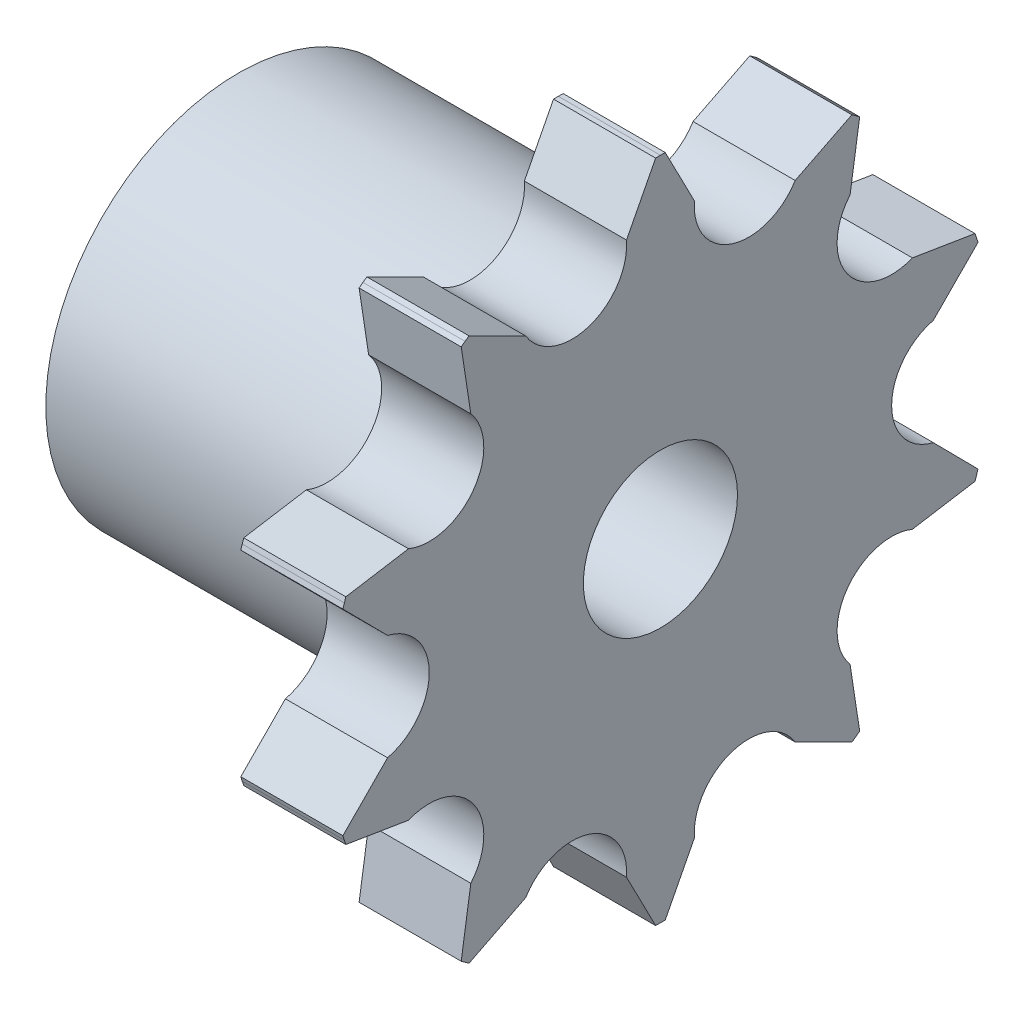
SolidWorks part; units mm, degrees
ref_plane "Front Plane" through (0, 0, 0) normal (0, 0, 1) x (1, 0, 0)
ref_plane "Top Plane" through (0, 0, 0) normal (0, 1, 0) x (1, 0, 0)
ref_plane "Right Plane" through (0, 0, 0) normal (1, 0, 0) x (0, 0, -1)
sketch "Sketch1" plane through (0, 0, 0) normal (1, 0, 0) x (0, 0, -1)
  line L0 (0, 0) -> (0, 17.25)
  line L1 (0, 0) -> (10.1393, 13.9555)
  line L4 (10.1393, 13.9555) -> (9.936, 14.101)
  line L5 (9.936, 14.101) -> (6.9922, 12.6205)
  line L6 (0, 0) -> (3.7082, 11.4127) construction
  line L7 (0.25, 17.2482) -> (1.7614, 14.3201)
  line L8 (10.1393, 13.9555) -> (10.2862, 14.1578)
  line L9 (0, 17.25) -> (0, 17.5)
  circle A0 centre (0, 0) radius 12
  circle A1 centre (0, 0) radius 17.25
  circle A2 centre (0, 0) radius 14.4281 construction
  arc A3 (1.7614, 14.3201) -> (6.9922, 12.6205) centre (4.5826, 14.1037) ccw
  circle A4 centre (0, 0) radius 17.5
  point P10 (10.0376, 14.0283)
  point P13 (0.125, 17.2491)
  dimension "D1" = 24
  dimension "D2" = 34.5
  dimension "D3" = 0.25
  dimension "D6" = 35
  dimension "D4" = 36
  dimension "D5" = 5.5
extrude "Boss-Extrude1" add sketch "Sketch1" along normal blind 5.3 contours L1 A0 L0 | A3 A0 L1 L4 L5 | A3 L7 A1 L0 A0 region at (0, 7.4839, -2.4317) region at (0, 13.8822, -0.9253) region at (0, 11.7748, -7.4111)
pattern_circular "CirPattern2" count 10 over 360 about axis through (5.3, 0, 0) along (-1, 0, 0) of "Boss-Extrude1" reverse direction yes
sketch "Sketch2" plane through (0, 0, 0) normal (-1, 0, 0) x (0, 0, 1)
  circle A0 centre (0, 0) radius 4
  circle A1 centre (0, 0) radius 10
  dimension "D1" = 8
  dimension "D2" = 20
extrude "Boss-Extrude2" add sketch "Sketch2" along normal blind 16.6
extrude "Cut-Extrude2" cut sketch "Sketch2<2>" against normal blind 16.6 contours A0 region at (0, 0, 0)
sketch "Sketch2<2>" plane through (0, 0, 0) normal (-1, 0, 0) x (0, 0, 1) same geometry as "Sketch2"
